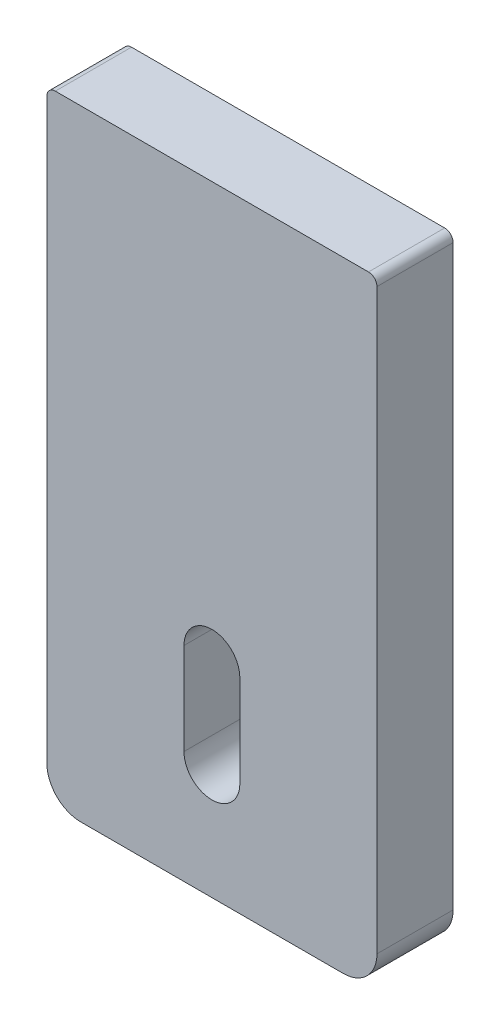
SolidWorks part; units mm, degrees
ref_plane "Front Plane" through (0, 0, 0) normal (0, 0, 1) x (1, 0, 0)
ref_plane "Top Plane" through (0, 0, 0) normal (0, 1, 0) x (1, 0, 0)
ref_plane "Right Plane" through (0, 0, 0) normal (1, 0, 0) x (0, 0, -1)
sketch "Sketch1" plane through (0, 0, 0) normal (0, 0, 1) x (1, 0, 0)
  line L0 (0, 0) -> (10, 0) construction
  line L1 (0, 0) -> (0, 10) construction
  line L2 (23.5124, -45.3134) -> (-19.7958, -27.0738) construction
  line L3 (-10, 21) -> (10, 21) construction
  line L4 (10, 21) -> (10, -39.6225) construction
  line L5 (-10, -31.1994) -> (-10, 21) construction
  line L6 (23.5124, -45.3134) -> (-19.7958, -27.0738) construction
  line L7 (-10, 21) -> (10, 21) construction
  line L8 (10, 21) -> (10, -39.6225) construction
  line L9 (-10, -31.1994) -> (-10, 21) construction
  line L10 (-1.65, -29.9856) -> (-1.65, -24.5603) construction
  line L11 (1.65, -24.5603) -> (1.65, -29.9856) construction
  line L12 (-1.65, -29.9856) -> (-1.65, -24.5603)
  line L13 (1.65, -24.5603) -> (1.65, -29.9856)
  line L14 (9.75, -36.6356) -> (9.75, 0)
  line L15 (9.75, 0) -> (-9.75, 0)
  line L16 (-9.75, 0) -> (-9.75, -36.6356)
  line L17 (-9.75, -36.6356) -> (9.75, -36.6356)
  line L18 (0, -31.6356) -> (0, -36.6356) construction
  line L19 (0, 0) -> (0, -10) construction
  circle A0 centre (0, 0) radius 10 construction
  circle A1 centre (0, 0) radius 10 construction
  arc A2 (1.65, -24.5603) -> (-1.65, -24.5603) centre (0, -24.5603) ccw construction
  arc A3 (-1.65, -29.9856) -> (1.65, -29.9856) centre (0, -29.9856) ccw construction
  arc A4 (1.65, -24.5603) -> (-1.65, -24.5603) centre (0, -24.5603) ccw
  arc A5 (-1.65, -29.9856) -> (1.65, -29.9856) centre (0, -29.9856) ccw
  dimension "D1" = 0.5
  dimension "D2" = 5
  dimension "D3" = 10
extrude "Boss-Extrude1" add sketch "Sketch1" along normal blind 5
fillet "Fillet1" radius 2 2 edges at (-9.75, -36.6356, 2.5) (9.75, -36.6356, 2.5)
sketch "Sketch2" plane through (0, 0, 0) normal (0, 0, 1) x (1, 0, 0)
  line L0 (9.75, -36.6356) -> (9.75, 0) construction
  line L1 (9.75, 0) -> (-9.75, 0) construction
  line L2 (-9.75, 0) -> (-9.75, -36.6356) construction
  line L3 (9.75, -10) -> (9.75, 0)
  line L4 (9.75, 0) -> (-9.75, 0)
  line L5 (-9.75, 0) -> (-9.75, -10)
  line L6 (-9.75, -10) -> (9.75, -10)
  circle A0 centre (0, 0) radius 10 construction
extrude "Cut-Extrude1" cut sketch "Sketch2" along normal blind 0.5
fillet "Fillet2" radius 0.5 2 edges at (9.75, 0, 2.75) (-9.75, 0, 2.75)
chamfer "Chamfer1" distance 0.5 angle 45 5 edges at (-9.75, -22.3178, 0) (-9.1642, -36.0499, 0) (0, -36.6356, 0) (9.1642, -36.0499, 0) (9.75, -22.3178, 0)
